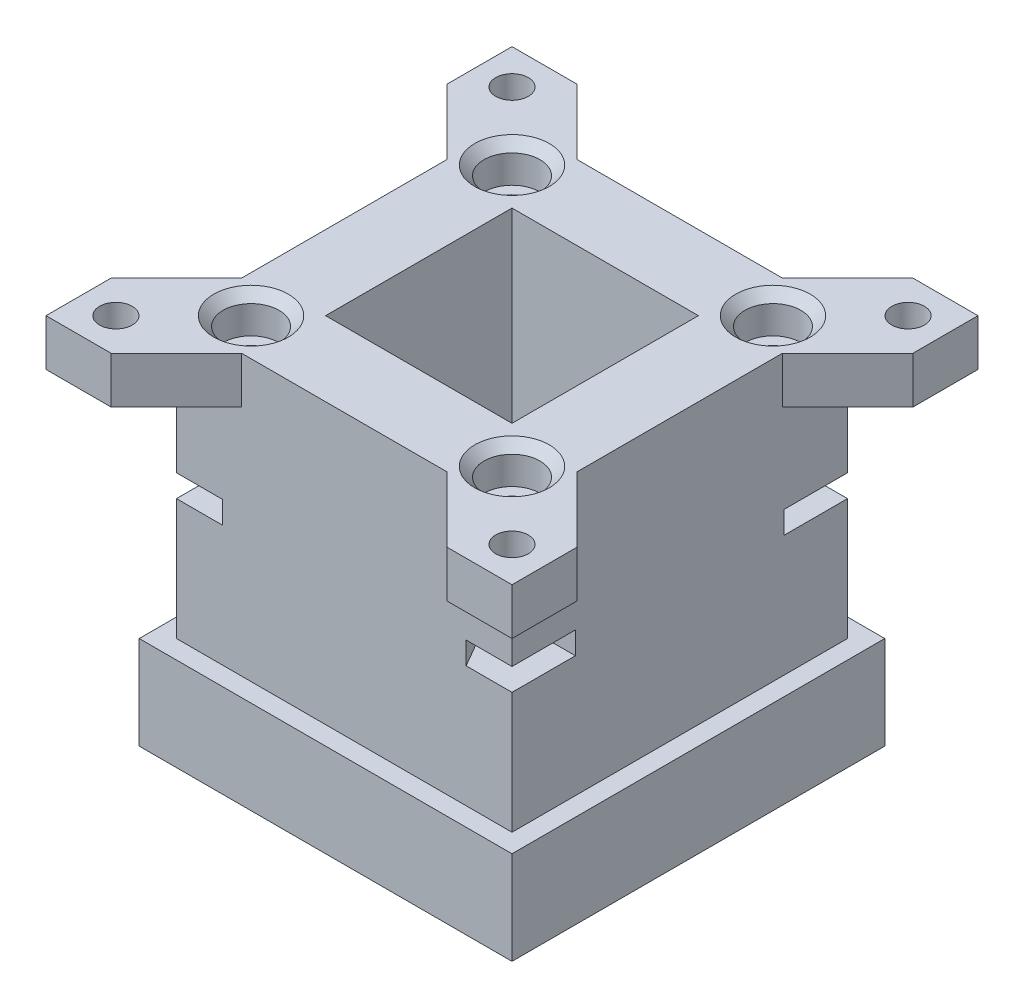
SolidWorks part; units mm, degrees
other "Markup1"
sketch "Sketch5" plane through (-30, 25, 30) normal (-0.0255, 0.5913, 0.806) x (0.9947, 0.0957, -0.0387)
ref_plane "Front Plane" through (0, 0, 0) normal (0, 0, 1) x (1, 0, 0)
ref_plane "Top Plane" through (0, 0, 0) normal (0, 1, 0) x (1, 0, 0)
ref_plane "Right Plane" through (0, 0, 0) normal (1, 0, 0) x (0, 0, -1)
ref_plane "Plane6" through (0, -5, 0) normal (0, 1, 0) x (1, 0, 0)
sketch "Sketch1" plane through (0, 0, 0) normal (0, 1, 0) x (1, 0, 0)
  line L1 (10, 10) -> (-10, 10)
  line L2 (10, 10) -> (10, -10)
  line L3 (10, -10) -> (-10, -10)
  line L4 (-10, 10) -> (-10, -10)
  line L5 (10, 10) -> (-10, -10) construction
  line L6 (10, -10) -> (-10, 10) construction
  line L7 (18, -18) -> (-18, -18)
  line L8 (18, -18) -> (18, 18)
  line L9 (18, 18) -> (-18, 18)
  line L10 (-18, -18) -> (-18, 18)
  line L11 (18, -18) -> (-18, 18) construction
  line L12 (18, 18) -> (-18, -18) construction
  point P0 (0, 0)
  point P1 (0, 0)
  dimension "D3" = 20
  dimension "D4" = 20
  dimension "D5" = 36
  dimension "D6" = 36
sketch "Sketch4" plane through (0, -5, 0) normal (0, 1, 0) x (1, 0, 0)
  line L25 (-2.5, -8.5481) -> (-2.5, -10)
  line L26 (7.5344, 0) -> (3.7672, 6.525)
  line L31 (3.7672, 6.525) -> (-3.7672, 6.525)
  line L32 (-3.7672, 6.525) -> (-7.5344, 0)
  line L35 (-7.5344, 0) -> (-3.7672, -6.525)
  line L36 (-3.7672, -6.525) -> (3.7672, -6.525)
  line L37 (3.7672, -6.525) -> (7.5344, 0)
  line L42 (10, 10) -> (2.5, 10)
  line L43 (10, 10) -> (10, 2.5)
  line L44 (10, -10) -> (2.5, -10)
  line L51 (-10, 10) -> (-10, 2.5)
  line L52 (10, 10) -> (-10, -10) construction
  line L53 (10, -10) -> (-10, 10) construction
  line L54 (20, 20) -> (-20, 20)
  line L55 (20, 20) -> (20, -20)
  line L56 (20, -20) -> (-20, -20)
  line L57 (-20, 20) -> (-20, -20)
  line L58 (20, 20) -> (-20, -20) construction
  line L59 (20, -20) -> (-20, 20) construction
  line L60 (8.4224, 2.5) -> (4.8441, 8.5694)
  line L61 (4.8441, 8.5694) -> (2.5, 8.5481)
  line L62 (-4.9993, 8.4799) -> (-8.3796, 2.5)
  line L63 (-8.4224, -2.5) -> (-4.8441, -8.5694)
  line L64 (-4.8441, -8.5694) -> (-2.5, -8.5481)
  line L65 (4.9993, -8.4799) -> (8.3796, -2.5)
  line L66 (2.5, -8.5026) -> (2.5, -10)
  line L67 (2.5, -8.5026) -> (4.9993, -8.4799)
  line L68 (-2.5, -10) -> (-10, -10)
  line L69 (-8.3796, 2.5) -> (-10, 2.5)
  line L70 (-8.4224, -2.5) -> (-10, -2.5)
  line L71 (2.5, 8.5481) -> (2.5, 10)
  line L72 (-2.5, 8.5026) -> (-2.5, 10)
  line L73 (8.3796, -2.5) -> (10, -2.5)
  line L74 (8.4224, 2.5) -> (10, 2.5)
  line L75 (-2.5, 8.5026) -> (-4.9993, 8.4799)
  line L76 (-10, -2.5) -> (-10, -10)
  line L77 (10, -2.5) -> (10, -10)
  line L78 (-2.5, 10) -> (-10, 10)
  circle A3 centre (0, 0) radius 6.525 construction
  circle A5 centre (0, 0) radius 8.525 construction
  point P42 (0, 0)
  dimension "D1" = 13.05
  dimension "D2" = 20
  dimension "D7" = 5
  dimension "D3" = 20
  dimension "D4" = 40
  dimension "D5" = 40
  dimension "D6" = 17.05
  dimension "D8" = 2.5
  dimension "D9" = 4
extrude "Boss-Extrude4" add sketch "Sketch1" along normal blind 35
ref_plane "Plane4" through (0, 30, 0) normal (0, 1, 0) x (1, 0, 0)
sketch "Sketch9" plane through (0, 30, 0) normal (0, 1, 0) x (1, 0, 0)
  line L5 (11, 11) -> (-11, 11)
  line L6 (11, 11) -> (11, -11)
  line L7 (25, -25) -> (-25, -25)
  line L8 (25, -25) -> (25, 25)
  line L9 (25, 25) -> (-25, 25)
  line L10 (-25, -25) -> (-25, 25)
  line L11 (25, -25) -> (-25, 25) construction
  line L12 (25, 25) -> (-25, -25) construction
  line L13 (11, -11) -> (-11, -11)
  line L14 (-11, 11) -> (-11, -11)
  line L15 (11, 11) -> (-11, -11) construction
  line L16 (11, -11) -> (-11, 11) construction
  point P0 (0, 0)
  point P1 (0, 0)
  dimension "D1" = 22
  dimension "D2" = 22
  dimension "D3" = 50
  dimension "D4" = 50
extrude "Boss-Extrude6" add sketch "Sketch9" along normal blind 5
ref_plane "Plane5" through (0, 25, 0) normal (0, 1, 0) x (1, 0, 0)
sketch "Sketch10" plane through (0, 25, 0) normal (0, 1, 0) x (1, 0, 0)
  line L0 (-25, 25) -> (-25, -25) construction
  line L1 (25, 25) -> (-25, 25) construction
  circle A6 centre (-21.25, 21.25) radius 1.75
  circle A7 centre (21.25, 21.25) radius 1.75
  circle A8 centre (21.25, -21.25) radius 1.75
  circle A9 centre (-21.25, -21.25) radius 1.75
  point P11 (0, 0)
  dimension "D1" = 3.5
  dimension "D2" = 3.75
  dimension "D3" = 3.75
extrude "Cut-Extrude2" cut sketch "Sketch10" along normal blind 10
sketch "Sketch11" plane through (0, 25, 0) normal (0, 1, 0) x (1, 0, 0)
  line L1 (11, 18) -> (-11, 18)
  line L2 (18, 11) -> (18, -11)
  line L3 (11, -18) -> (-11, -18)
  line L4 (-18, 11) -> (-18, -11)
  line L5 (18, 18) -> (-18, -18) construction
  line L6 (18, -18) -> (-18, 18) construction
  line L7 (-25, 25) -> (-25, -25) construction
  line L8 (-25, -18) -> (-25, 18)
  line L11 (25, 25) -> (-25, 25) construction
  line L12 (-18, 25) -> (18, 25)
  line L14 (25, 18) -> (25, -18)
  line L15 (25, -25) -> (25, 25) construction
  line L17 (18, -25) -> (-18, -25)
  line L18 (-25, -25) -> (25, -25) construction
  line L20 (-25, -18) -> (-18, -11)
  line L22 (18, -25) -> (11, -18)
  line L23 (25, -18) -> (18, -11)
  line L24 (-18, -25) -> (-11, -18)
  line L25 (-25, 18) -> (-18, 11)
  line L26 (-18, 25) -> (-11, 18)
  line L27 (18, 25) -> (11, 18)
  line L28 (25, 18) -> (18, 11)
  point P0 (0, 0)
  dimension "D1" = 36
  dimension "D2" = 36
extrude "Cut-Extrude3" cut sketch "Sketch11" along normal blind 10
extrude "Boss-Extrude7" add sketch "Sketch4" along normal blind 10
ref_plane "Plane7" through (0, 35, 0) normal (0, 1, 0) x (1, 0, 0)
sketch "Sketch12" plane through (0, 35, 0) normal (0, 1, 0) x (1, 0, 0)
  line L0 (10, 10) -> (-10, 10) construction
  line L1 (-18, -18) -> (-18, 18) construction
  line L4 (0, 10) -> (0, -10) construction
  line L5 (-10, -10) -> (10, -10) construction
  line L6 (-10, 0) -> (10, 0) construction
  line L7 (-10, 10) -> (-10, -10) construction
  line L8 (10, -10) -> (10, 10) construction
  circle A0 centre (-14, 14) radius 3
  circle A1 centre (14, 14) radius 3
  circle A2 centre (-14, -14) radius 3
  circle A3 centre (14, -14) radius 3
  dimension "D1" = 6
  dimension "D2" = 4
  dimension "D3" = 4
extrude "Cut-Extrude4" cut sketch "Sketch12" against normal blind 4
chamfer "Chamfer1" distance 1 angle 45 4 edges at (-14, 35, -11) (-14, 35, 11) (14, 35, 17) (14, 35, -17)
ref_plane "Plane8" through (0, 31, 0) normal (0, 1, 0) x (1, 0, 0)
sketch "Sketch13" plane through (0, 31, 0) normal (0, 1, 0) x (1, 0, 0)
  line L0 (0, 10) -> (0, -10) construction
  line L1 (-2.5, 10) -> (2.5, 10) construction
  line L2 (-10, -10) -> (10, -10) construction
  line L3 (-10, 0) -> (10, 0) construction
  line L4 (-10, -2.5) -> (-10, 2.5) construction
  line L5 (10, -10) -> (10, 10) construction
  circle A0 centre (-14, 14) radius 1.75
  circle A1 centre (14, 14) radius 1.75
  circle A2 centre (14, -14) radius 1.75
  circle A3 centre (-14, -14) radius 1.75
  dimension "D1" = 3.5
extrude "Cut-Extrude5" cut sketch "Sketch13" against normal blind 13
ref_plane "Plane9" through (0, 18, 0) normal (0, 1, 0) x (1, 0, 0)
sketch "Sketch15" plane through (0, 18, 0) normal (0, 1, 0) x (1, 0, 0)
  line L0 (0, 10) -> (0, -10) construction
  line L1 (-10.7668, 14) -> (-12.3834, 16.8)
  line L5 (-15.6166, 11.2) -> (-12.3834, 11.2)
  line L6 (-12.3834, 11.2) -> (-10.7668, 14)
  line L7 (10, 10) -> (-10, 10) construction
  line L8 (-10, -10) -> (10, -10) construction
  line L9 (-10, 0) -> (10, 0) construction
  line L10 (-10, -2.5) -> (-10, 2.5) construction
  line L11 (10, -10) -> (10, 10) construction
  line L14 (15.6166, 11.2) -> (12.3834, 11.2)
  line L15 (12.3834, 11.2) -> (10.7668, 14)
  line L16 (10.7668, 14) -> (12.3834, 16.8)
  line L18 (15.6166, -11.2) -> (12.3834, -11.2)
  line L22 (10.7668, -14) -> (12.3834, -16.8)
  line L23 (12.3834, -11.2) -> (10.7668, -14)
  line L24 (-15.6166, -11.2) -> (-12.3834, -11.2)
  line L25 (-12.3834, -11.2) -> (-10.7668, -14)
  line L26 (-10.7668, -14) -> (-12.3834, -16.8)
  line L30 (-15.6166, 11.2) -> (-22.1497, 11.2)
  line L31 (-22.1497, 11.2) -> (-24.4849, 19.968)
  line L32 (-24.4849, 19.968) -> (-15.5815, 22.3393)
  line L33 (15.6166, 11.2) -> (22.1497, 11.2)
  line L35 (-12.3834, 16.8) -> (-15.5815, 22.3393)
  line L36 (22.1497, 11.2) -> (24.4849, 19.968)
  line L37 (-16.4249, 12.6) -> (-15.6166, 11.2) [skipped]
  line L38 (-15.6166, 16.8) -> (-16.4249, 15.4) [skipped]
  line L39 (-12.3834, 16.8) -> (-14, 16.8) [skipped]
  line L40 (24.4849, 19.968) -> (15.5815, 22.3393)
  line L41 (12.3834, 16.8) -> (15.5815, 22.3393)
  line L42 (-15.6166, -11.2) -> (-22.1497, -11.2)
  line L43 (-22.1497, -11.2) -> (-24.4849, -19.968)
  line L44 (-24.4849, -19.968) -> (-15.5815, -22.3393)
  line L45 (-12.3834, -16.8) -> (-15.5815, -22.3393)
  line L46 (15.6166, -11.2) -> (22.1497, -11.2)
  line L47 (22.1497, -11.2) -> (24.4849, -19.968)
  line L48 (12.3834, -16.8) -> (15.5815, -22.3393)
  line L49 (24.4849, -19.968) -> (15.5815, -22.3393)
  circle A0 centre (-14, 14) radius 2.8 construction
extrude "Cut-Extrude7" cut sketch "Sketch15" along normal blind 2.4
equation "\"BallBearingDiameter\" = 22mm"
equation "\"SmallTubeOD\" = 75mm"
equation "\"SmallTubeID\"= \"SmallTubeOD\" - \"WallThickness\" * 2"
equation "\"ZTravel\"= 20mm"
equation "\"WallThickness\"= 5mm"
equation "\"RestrictingFlangeOD\"= \"SmallTubeOD\" + 10mm"
equation "\"HexNutDiameter\" = 13mm"
